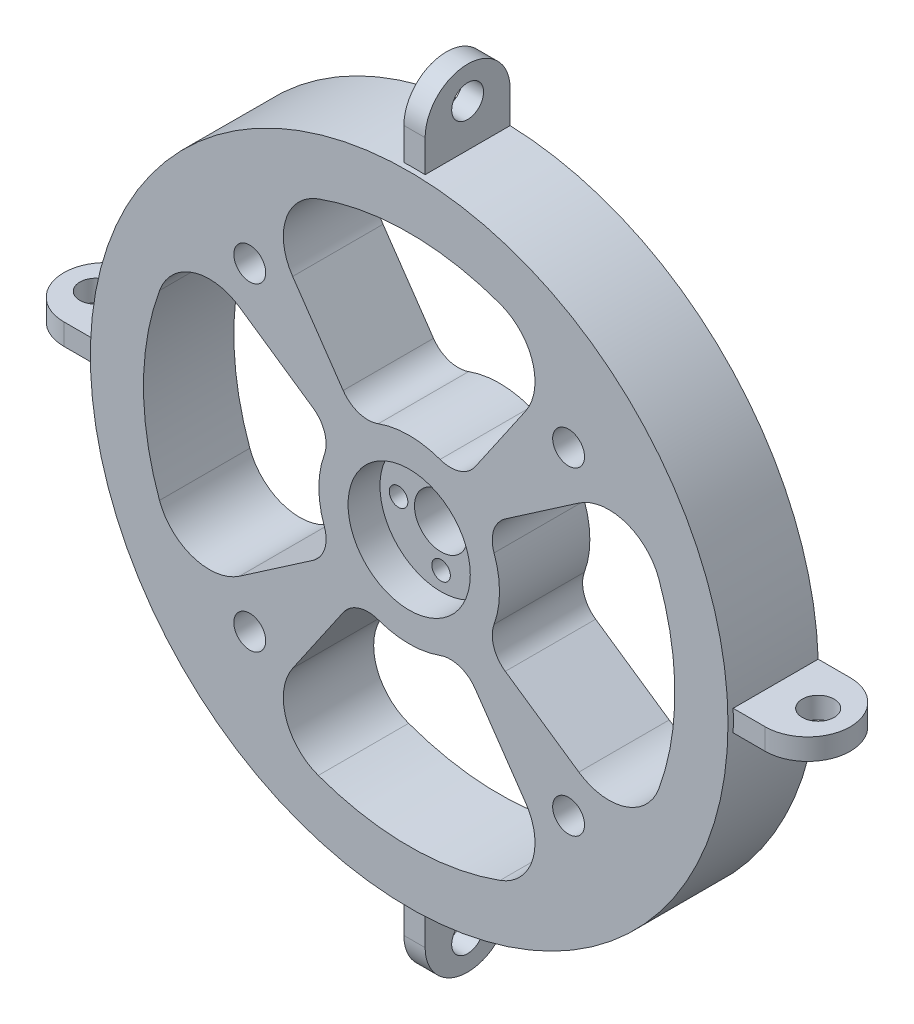
SolidWorks part; units mm, degrees
material "ABS"
ref_plane "前视基准面" through (0, 0, 0) normal (0, 0, 1) x (1, 0, 0)
ref_plane "上视基准面" through (0, 0, 0) normal (0, 1, 0) x (1, 0, 0)
ref_plane "右视基准面" through (0, 0, 0) normal (1, 0, 0) x (0, 0, -1)
sketch "草图1" plane through (0, 0, 0) normal (0, 0, 1) x (1, 0, 0)
  circle A0 centre (0, 0) radius 60
  dimension "D1" = 120
extrude "凸台-拉伸1" add sketch "草图1" along normal blind 17
sketch "草图2" plane through (0, 0, 17) normal (0, 0, 1) x (1, 0, 0)
  line L0 (0, 30) -> (0, 0) construction
  line L1 (0, 0) -> (0, -30) construction
  line L2 (-30, 0) -> (0, 0) construction
  line L3 (0, 0) -> (30, 0) construction
  circle A4 centre (-30, 30) radius 3
  circle A5 centre (30, 30) radius 3
  circle A6 centre (30, -30) radius 3
  circle A7 centre (-30, -30) radius 3
  dimension "D1" = 6
  dimension "D2" = 6
  dimension "D7" = 6
  dimension "D8" = 6
  dimension "D3" = 30
  dimension "D4" = 30
  dimension "D5" = 30
  dimension "D6" = 30
  dimension "D9" = 60
  dimension "D10" = 60
extrude "切除-拉伸1" cut sketch "草图2" against normal through all
sketch "草图3" plane through (0, 0, 0) normal (1, 0, 0) x (0, 0, -1)
  line L0 (0, 58) -> (-16, 58)
  line L1 (-16, 58) -> (-16, 66)
  line L2 (0, 66) -> (0, 58)
  line L3 (0, 0) -> (-35.6052, 0) construction
  arc A0 (-16, 66) -> (0, 66) centre (-8, 66) cw
  dimension "D3" = 8
  dimension "D1" = 58
  dimension "D2" = 8
  dimension "D4" = 0
extrude "凸台-拉伸2" add sketch "草图3" along normal blind 2 and the other way blind 2
sketch "草图4" plane through (2, 0, 0) normal (1, 0, 0) x (0, 0, -1)
  line L0 (-16, 59.9667) -> (0, 59.9667) construction
  line L1 (0, 59.9667) -> (0, 66) construction
  circle A0 centre (-8, 67.9667) radius 3
  dimension "D1" = 6
  dimension "D2" = 8
  dimension "D3" = 8
extrude "切除-拉伸7" cut sketch "草图4" against normal through all
sketch "草图5" plane through (0, 0, 0) normal (0, 0, -1) x (-1, 0, 0)
  circle A0 centre (0, 0) radius 5
  dimension "D1" = 10
extrude "切除-拉伸3" cut sketch "草图5" against normal up to next
sketch "草图6" plane through (0, 0, 17) normal (0, 0, 1) x (1, 0, 0)
  circle A0 centre (0, 0) radius 11.5
  dimension "D1" = 23
extrude "切除-拉伸4" cut sketch "草图6" against normal blind 6
sketch "草图7" plane through (0, 0, 11) normal (0, 0, 1) x (1, 0, 0)
  circle A0 centre (0, 0) radius 8 construction
  circle A1 centre (-8, 0) radius 1.75
  circle A2 centre (0, 8) radius 1.75
  circle A3 centre (8, 0) radius 1.75
  circle A4 centre (0, -8) radius 1.75
  dimension "D1" = 16
  dimension "D2" = 3.5
  dimension "D3" = 3.5
  dimension "D4" = 3.5
  dimension "D5" = 3.5
extrude "切除-拉伸5" cut sketch "草图7" against normal up to next
sketch "草图8" plane through (0, 0, 17) normal (0, 0, 1) x (1, 0, 0)
  line L0 (-37.5877, -13.6808) -> (0, 0) construction
  line L1 (0, 0) -> (-37.5877, 13.6808) construction
  line L2 (0, 0) -> (-30, 0) construction
  line L3 (-37.5877, -13.6808) -> (-46.9846, -17.101) construction
  line L4 (-37.5877, 13.6808) -> (-46.9846, 17.101) construction
  line L13 (-18.0919, -12.4238) -> (0, 0) construction
  line L14 (-18.0919, 12.4238) -> (-31.9269, 21.9243)
  line L15 (-31.9269, -21.9243) -> (-18.0919, -12.4238)
  arc A0 (-37.5877, -13.6808) -> (-37.5877, 13.6808) centre (0, 0) cw construction
  arc A6 (-46.9846, -17.101) -> (-46.9846, 17.101) centre (0, 0) cw
  arc A7 (-46.9846, -17.101) -> (-31.9269, -21.9243) centre (-37.5877, -13.6808) ccw
  arc A9 (-15.9748, -5.8143) -> (-15.9748, 5.8143) centre (0, 0) cw
  arc A11 (-15.9748, -5.8143) -> (-18.0919, -12.4238) centre (-21.2997, -7.7525) cw
  arc A31 (-15.9748, 5.8143) -> (-18.0919, 12.4238) centre (-21.2997, 7.7525) ccw
  arc A32 (-46.9846, 17.101) -> (-31.9269, 21.9243) centre (-37.5877, 13.6808) cw
  dimension "D2" = 20
  dimension "D3" = 40
  dimension "D4" = 50
  dimension "D5" = 17
extrude "切除-拉伸6" cut sketch "草图8" against normal up to next
pattern_circular "阵列(圆周)3" count 4 over 360 about axis through (0, 0, 17) along (0, 0, 1) of "切除-拉伸6"
pattern_circular "阵列(圆周)4" count 4 over 360 about axis through (0, 0, 17) along (0, 0, 1) of "凸台-拉伸2", "切除-拉伸7"
